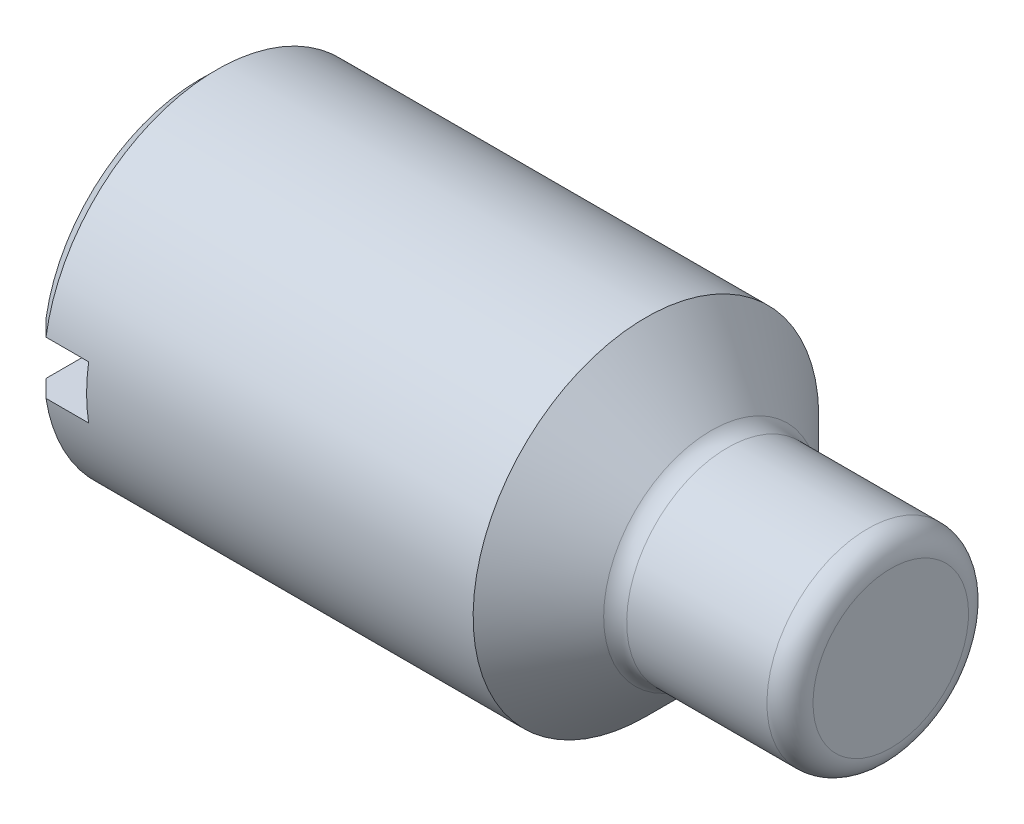
SolidWorks part; units mm, degrees
ref_plane "Front" through (0, 0, 0) normal (0, 0, 1) x (1, 0, 0)
ref_plane "Top" through (0, 0, 0) normal (0, 1, 0) x (1, 0, 0)
ref_plane "Right" through (0, 0, 0) normal (1, 0, 0) x (0, 0, -1)
sketch "Sketch1" plane through (0, 0, 0) normal (0, 0, 1) x (1, 0, 0)
  line L0 (6, 0) -> (0, 0)
  line L1 (6, 0) -> (6, 0.875)
  line L2 (6, 0.875) -> (4.5, 0.875)
  line L3 (4.5, 0.875) -> (3.875, 1.5)
  line L4 (3.875, 1.5) -> (0, 1.5)
  line L5 (-8.5703, 0) -> (3.0325, 0) construction
  line L7 (0, 1.5) -> (0, 0)
  dimension "D1" = 45
revolve "Base" add sketch "Sketch1" angle 360 about L5
cosmetic thread "ThreadCosmetic1" [suppressed] parameters "D1"=2.7
sketch "Sketch2" plane through (0, 0, 0) normal (0, 0, 1) x (1, 0, 0)
  line L0 (0, 1.5) -> (0, -1.5) construction
  line L1 (0, 0.23) -> (0.52, 0.23)
  line L2 (0, 0.23) -> (0, -0.23)
  line L3 (0, -0.23) -> (0.52, -0.23)
  line L4 (0.52, 0.23) -> (0.52, -0.23)
  dimension "t" = 0.52
  dimension "m" = 0.23
extrude "Notch" cut sketch "Sketch2" against normal through all and the other way through all
fillet "Fillet1" radius 0.2 2 edges at (6, -0.875, 0) (4.5, -0.875, 0)
chamfer "Chamfer1" distance 0.15 angle 45 2 edges at (0, 1.5, 0) (0, -1.5, 0)
sketch "Sketch3" plane through (0, 0, 0) normal (0, 0, 1) x (1, 0, 0)
  line L0 (0.15, 1.3701) -> (0.225, 1.5)
  line L1 (0.225, 1.5) -> (0.225, 1.65)
  line L2 (0.225, 1.65) -> (0.075, 1.65)
  line L3 (0.075, 1.65) -> (0.075, 1.5)
  line L4 (0.075, 1.5) -> (0.15, 1.3701)
  line L5 (0, 0) -> (1.285, 0) construction
  line L7 (0, 1.35) -> (0, 0.23) construction
  dimension "D2" = 0.15
  dimension "D3" = 0.15
revolve "Cut-Revolve10" [suppressed] cut sketch "Sketch3" angle 360 about L5
pattern_linear "LPattern10" [suppressed] count 24 spacing 0.18 along (1, 0, 0) of bodies 103
equation "\"D1@Chamfer1\" = (  \"d@Sketch1\" - \"D1@ThreadCosmetic1\" )  / 2"
equation "\"m@Sketch2\" = \"n@Sketch2\" / 2"
equation "\"D3@Sketch3\" = \"D1@Chamfer1\""
equation "\"D1@Sketch3\" = \"d@Sketch1\""
equation "\"D2@Sketch3\" =  ( \"d@Sketch1\" - \"D1@ThreadCosmetic1\" )  / 2"
equation "\"D3@LPattern10\" = \"D2@Sketch3\" * 1.2"
equation "\"D1@LPattern10\" =  ( \"l@Sketch1\" - \"z@Sketch1\" - \"D1@Chamfer1\" )  / \"D3@LPattern10\""
